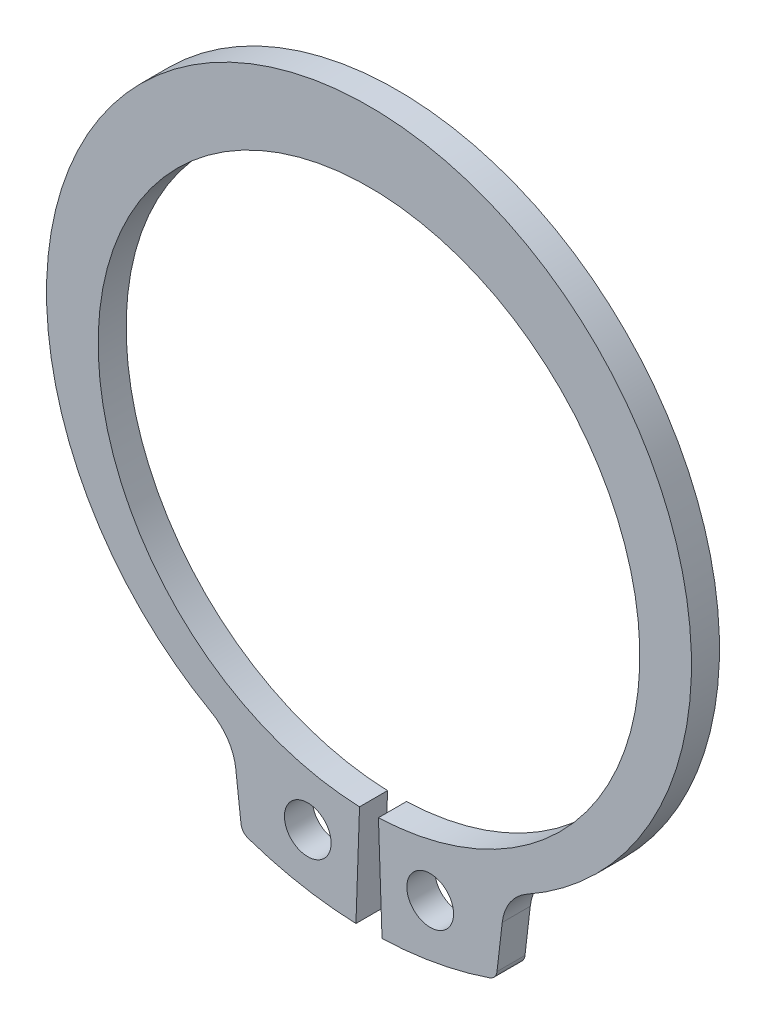
SolidWorks part; units mm, degrees
ref_plane "Front Plane" through (0, 0, 0) normal (0, 0, 1) x (1, 0, 0)
ref_plane "Top Plane" through (0, 0, 0) normal (0, 1, 0) x (1, 0, 0)
ref_plane "Right Plane" through (0, 0, 0) normal (1, 0, 0) x (0, 0, -1)
sketch "Sketch1" plane through (0, 0, 0) normal (0, 0, 1) x (1, 0, 0)
  line L0 (0, 1.6085) -> (-10.0459, -4.1915) construction
  line L1 (0, 12.15) -> (0, -14.3915) construction
  line L2 (-5.4478, -13.4459) -> (-5.8345, -10.1205) construction
  line L3 (0, 16.2085) -> (0, 13.2085)
  line L4 (-5.8345, -10.1205) -> (-6.5026, -11.4635) construction
  line L5 (-5.8345, -10.1205) -> (0, 1.6085) construction
  line L6 (0, 13.2085) -> (0, 16.2085) construction
  line L7 (0, 16.2085) -> (0, 14.7085) construction
  line L8 (0, -9.9915) -> (0, -14.3915) construction
  line L9 (-3.0403, -14.11) -> (0, 1.6085) construction
  line L10 (0, 1.6085) -> (-0.5587, -14.3915) construction
  line L11 (-5.4478, -13.4459) -> (0, 1.6085) construction
  line L12 (-5.7251, -11.0617) -> (-6.6791, -9.691) construction
  line L13 (-6.2021, -10.3763) -> (-5.8345, -10.1205) construction
  line L14 (-2.2029, -9.7805) -> (-3.0403, -14.11) construction
  line L15 (-2.6216, -11.9452) -> (-1.6398, -12.1351) construction
  line L16 (-0.5587, -14.3915) -> (-0.4048, -9.9845)
  line L17 (-5.4478, -13.4459) -> (-5.8345, -10.1205)
  arc A0 (0, 16.2085) -> (-5.8345, -10.1205) centre (0, 2.3975) ccw construction
  circle A2 centre (0, 1.6085) radius 14.6 construction
  arc A3 (-5.4478, -13.4459) -> (-0.5587, -14.3915) centre (0, 1.6085) ccw construction
  circle A4 centre (0, 1.6085) radius 11.6 construction
  circle A6 centre (-2.6216, -11.9452) radius 1 construction
  arc A7 (-6.6791, -9.691) -> (-5.7251, -11.0617) centre (-7.5924, -11.344) cw construction
  circle A9 centre (0, 1.6085) radius 12.5 construction
  circle A10 centre (0, 1.6085) radius 11.95 construction
  circle A11 centre (-2.6216, -11.9452) radius 1
  arc A12 (-0.5587, -14.3915) -> (-5.4478, -13.4459) centre (0, 1.6085) cw
  arc A13 (0, 13.2085) -> (-0.4048, -9.9845) centre (0, 1.6085) ccw
  arc A14 (-5.8345, -10.1205) -> (0, 16.2085) centre (0, 2.3975) cw
  point P5 (-10.0459, -4.1915)
  point P24 (-4.9681, -12.1203)
  point P35 (0, 16.2085)
  point P36 (0, 13.2085)
  point P37 (0, -9.9915)
  point P38 (0, -14.3915)
  dimension "Hole Diameter" = 2
  dimension "D10" = 1.8886
  dimension "For OD" = 25
  dimension "ID" = 23.2
  dimension "Max Sec." = 3
  dimension "Lug Height" = 4.4
  dimension "D6" = 2
  dimension "D5" = 3.3478
  dimension "D8" = 1.67
  dimension "D3" = 120
  dimension "D2" = 5
  dimension "D4" = 1.67
extrude "Boss-Extrude1" add sketch "Sketch1" along normal blind 1.2
fillet "Fillet1" radius 2.07 1 edges at (-5.8345, -10.1205, 0.6)
fillet "Fillet4" radius 0.47 1 edges at (-5.4478, -13.4459, 0.6)
mirror "Mirror1" about plane through (0, 16.2085, 1.2) normal (-1, 0, 0) of "Fillet1", "Fillet4", "Boss-Extrude1"
equation "\"For Groove Diameter@Sketch1\"=\"groove_d\""
equation "\"For OD@Sketch1\"=\"shaft_od\""
equation "\"Max Sec.@Sketch1\"=\"top_width\""
equation "\"ID@Sketch1\"=\"inner_d\""
equation "\"Lug Height@Sketch1\"=\"lug_height\""
equation "\"Hole Diameter@Sketch1\"=\"hole_d\""
equation "\"D3@Sketch1\"=\"angle\""
equation "\"D6@Sketch1\"=\"lug_inner_angle\""
equation "\"D2@Sketch1\"=\"lug_width\""
equation "\"D4@Sketch1\"=\"edge_width2\""
equation "\"D8@Sketch1\"=\"edge_width\""
equation "\"groove_d\"=23.90"
equation "\"shaft_od\"=25.00"
equation "\"inner_d\"=23.20"
equation "\"top_width\"=3.00"
equation "\"lug_height\"=4.40"
equation "\"hole_d\"=2.00"
equation "\"lug_inner_angle\"=2.00"
equation "\"lug_width\"=5.00"
equation "\"lug_height2\"=3.35"
equation "\"lug_radius\"=0.47"
equation "\"edge_width\"=1.67"
equation "\"edge_width2\"=1.67"
equation "\"edge_radius\"=2.07"
equation "\"angle\"=120.00"
equation "\"groove_t\"=1.30"
equation "\"ring_thickness\"=1.20"
equation "\"D1@Boss-Extrude1\"=\"ring_thickness\""
equation "\"D1@Fillet1\"=\"edge_radius\""
equation "\"D1@Fillet4\"=\"lug_radius\""
